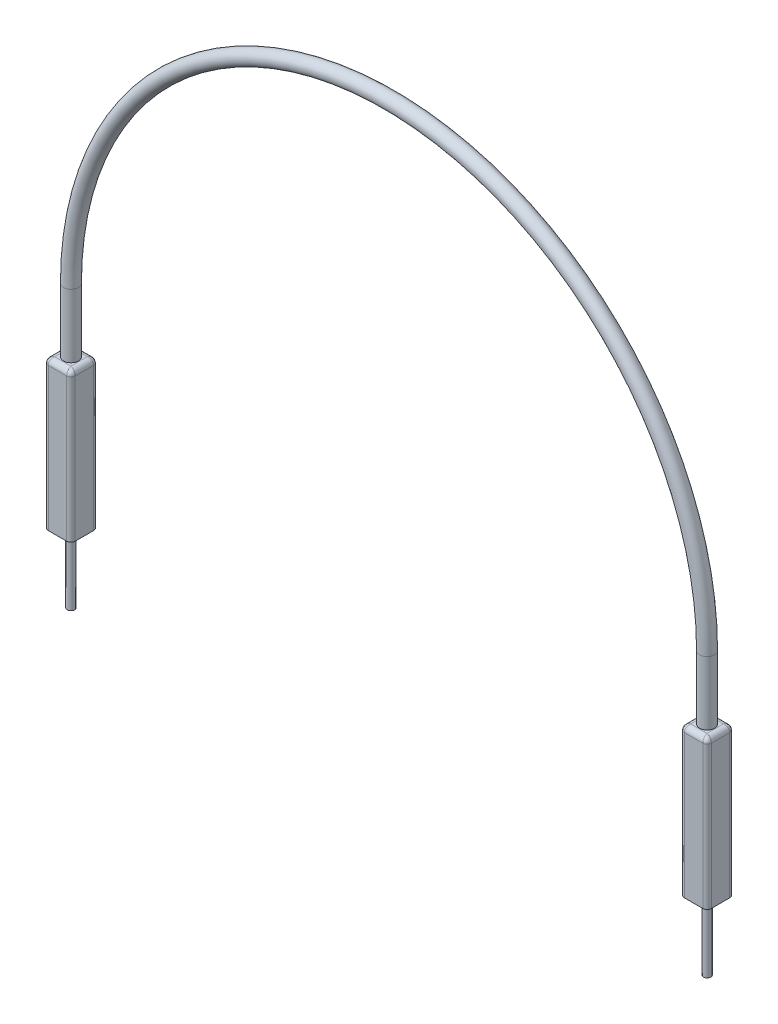
SolidWorks part; units mm, degrees
ref_plane "Front Plane" through (0, 0, 0) normal (0, 0, 1) x (1, 0, 0)
ref_plane "Top Plane" through (0, 0, 0) normal (0, 1, 0) x (1, 0, 0)
ref_plane "Right Plane" through (0, 0, 0) normal (1, 0, 0) x (0, 0, -1)
sketch "Sketch1" plane through (0, 0, 0) normal (0, 1, 0) x (1, 0, 0)
  line L0 (-30, 0) -> (30, 0) construction
  line L1 (-30, 1.27) -> (-30, -1.27) construction
  line L2 (-31.27, 1.27) -> (-28.73, 1.27)
  line L3 (-31.27, 1.27) -> (-31.27, -1.27)
  line L4 (-31.27, -1.27) -> (-28.73, -1.27)
  line L5 (-28.73, 1.27) -> (-28.73, -1.27)
  line L6 (30, 1.27) -> (30, -1.27) construction
  line L7 (28.73, 1.27) -> (31.27, 1.27)
  line L8 (28.73, 1.27) -> (28.73, -1.27)
  line L9 (28.73, -1.27) -> (31.27, -1.27)
  line L10 (31.27, 1.27) -> (31.27, -1.27)
  dimension "D1" = 60
  dimension "D2" = 2.54
  dimension "D3" = 2.54
  dimension "D4" = 2.54
  dimension "D5" = 2.54
extrude "SET WIDTH" add sketch "Sketch1" along normal blind 14
sketch "Sketch2" plane through (0, 0, 0) normal (0, 0, 1) x (1, 0, 0)
  line L0 (-30, 14) -> (-30, 0) construction
  line L1 (-31.27, 14) -> (-28.73, 14) construction
  line L2 (-31.27, 0) -> (-28.73, 0) construction
  line L3 (30, 14) -> (30, 0) construction
  line L4 (28.73, 14) -> (31.27, 14) construction
  line L5 (28.73, 0) -> (31.27, 0) construction
  line L6 (0, 0) -> (0, 50) construction
  line L7 (-30, 14) -> (-30, 20)
  line L8 (30, 14) -> (30, 20)
  arc A0 (-30, 20) -> (30, 20) centre (0, 20) cw
  dimension "D1" = 50
sketch "Sketch3" plane through (0, 14, 0) normal (0, 1, 0) x (1, 0, 0)
  circle A0 centre (-30, 0) radius 0.7
  dimension "D1" = 1.4
sweep "Wire Height" add profiles "Sketch3" path "Sketch2"
fillet "Fillet2" radius 0.4 8 edges at (31.27, 7, -1.27) (31.27, 7, 1.27) (28.73, 7, -1.27) (28.73, 7, 1.27) (-31.27, 7, -1.27) (-31.27, 7, 1.27) (-28.73, 7, 1.27) (-28.73, 7, -1.27)
fillet "Fillet3" radius 0.5 16 edges at (28.8472, 14, 1.1528) (28.73, 14, 0) (28.8472, 14, -1.1528) (30, 14, -1.27) (31.1528, 14, -1.1528) (31.27, 14, 0) (31.1528, 14, 1.1528) (-31.1528, 14, 1.1528) (-31.27, 14, 0) (-31.1528, 14, -1.1528) (-30, 14, -1.27) (-28.8472, 14, -1.1528) (-28.73, 14, 0) (-28.8472, 14, 1.1528) (30, 14, 1.27) (-30, 14, 1.27)
sketch "Sketch4" plane through (0, 0, 0) normal (0, -1, 0) x (1, 0, 0)
  circle A0 centre (-30, 0) radius 0.35
  circle A1 centre (30, 0) radius 0.35
  dimension "D1" = 0.7
extrude "Boss-Extrude2" add sketch "Sketch4" along normal blind 6.5
